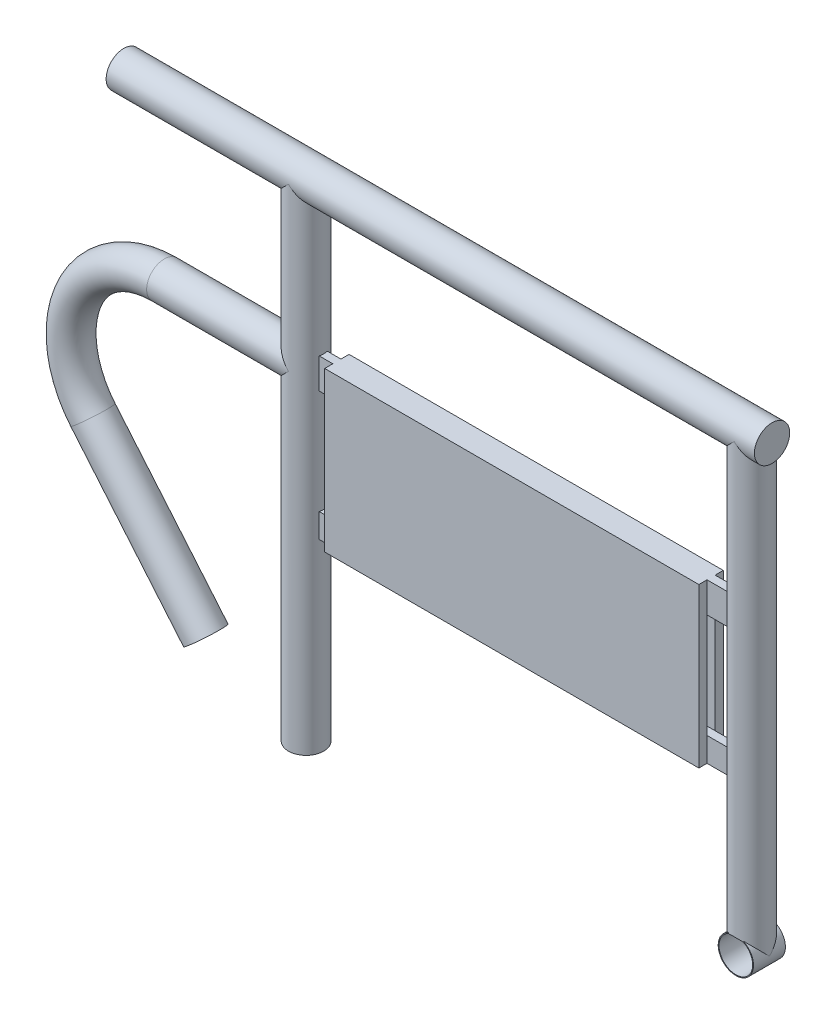
SolidWorks part; units mm, degrees
ref_plane "Front Plane" through (0, 0, 0) normal (0, 0, 1) x (1, 0, 0)
ref_plane "Top Plane" through (0, 0, 0) normal (0, 1, 0) x (1, 0, 0)
ref_plane "Right Plane" through (0, 0, 0) normal (1, 0, 0) x (0, 0, -1)
sketch "Sketch1" plane through (0, 0, 0) normal (0, 1, 0) x (1, 0, 0)
  circle A0 centre (0, 0) radius 11.065
  circle A1 centre (279.4, 0) radius 11.065
  dimension "D1" = 22.13
  dimension "D2" = 22.13
  dimension "D3" = 279.4
extrude "Extrude1" add sketch "Sketch1" along normal blind 279.4
sketch "Sketch2" plane through (0, 0, 0) normal (1, 0, 0) x (0, 0, -1)
  line L0 (11.065, 279.4) -> (-11.065, 279.4) construction
  circle A0 centre (0, 279.4) radius 11.065
extrude "Extrude2" add sketch "Sketch2" along normal blind 292.1 and the other way blind 114.3
sketch "Sketch3" plane through (-114.3, 0, 0) normal (-1, 0, 0) x (0, 0, 1)
  circle A0 centre (0, 177.8) radius 11.065
  circle A1 centre (0, 279.4) radius 11.065 construction
  dimension "D1" = 101.6
extrude "Extrude3" add sketch "Sketch3" against normal blind 114.3
sketch "Sketch5" plane through (0, 0, 0) normal (0, 0, 1) x (1, 0, 0)
  line L0 (-114.3, 188.865) -> (-114.3, 166.735) construction
  line L1 (-139.7, 188.865) -> (-88.9, 188.865)
  line L2 (-139.7, 188.865) -> (-139.7, 166.735)
  line L3 (-139.7, 166.735) -> (-88.9, 166.735)
  line L4 (-88.9, 188.865) -> (-88.9, 166.735)
  line L5 (-139.7, 188.865) -> (-88.9, 166.735) construction
  line L6 (-139.7, 166.735) -> (-88.9, 188.865) construction
  line L7 (-114.3, 166.735) -> (-11.065, 166.735) construction
  point P0 (-114.3, 177.8)
  dimension "D1" = 25.4
extrude "Extrude5" cut sketch "Sketch5" against normal through all and the other way through all
sketch "Sketch7" plane through (-88.9, 0, 0) normal (-1, 0, 0) x (0, 0, 1)
  line L0 (0, 119.38) -> (28.8371, 119.38)
  circle A0 centre (0, 177.8) radius 11.065
  dimension "D1" = 58.42
revolve "Revolve-Thin3" add sketch "Sketch7" angle 130 about L0 body kept at (11.065, 0, 0) wall 10
sketch "Sketch10" plane through (-95.5145, 113.8298, 0) normal (0.6428, -0.766, 0) x (0.766, 0.6428, 0)
  circle A0 centre (-49.7854, 0) radius 11.065
extrude "Extrude6" add sketch "Sketch10" along normal blind 110.1
sketch "Sketch11" plane through (0, 0, 0) normal (1, 0, 0) x (0, 0, -1)
  line L1 (2.55, 168.275) -> (-2.55, 168.275)
  line L2 (2.55, 168.275) -> (2.55, 187.325)
  line L3 (2.55, 187.325) -> (-2.55, 187.325)
  line L4 (-2.55, 168.275) -> (-2.55, 187.325)
  line L5 (2.55, 168.275) -> (-2.55, 187.325) construction
  line L6 (2.55, 187.325) -> (-2.55, 168.275) construction
  line L7 (2.55, 87.6717) -> (-2.55, 87.6717)
  line L8 (2.55, 87.6717) -> (2.55, 102.8283)
  line L9 (2.55, 102.8283) -> (-2.55, 102.8283)
  line L10 (-2.55, 87.6717) -> (-2.55, 102.8283)
  line L11 (2.55, 87.6717) -> (-2.55, 102.8283) construction
  line L12 (2.55, 102.8283) -> (-2.55, 87.6717) construction
  point P0 (0, 177.8)
  point P6 (0, 95.25)
  dimension "D1" = 19.05
  dimension "D2" = 5.1
  dimension "D3" = 82.55
extrude "Extrude7" add sketch "Sketch11" along normal blind 279.4
sketch "Sketch12" plane through (0, 0, 2.55) normal (0, 0, 1) x (1, 0, 0)
  line L0 (268.6328, 187.325) -> (10.7672, 187.325) construction
  line L1 (19.2926, 187.325) -> (253.8741, 187.325)
  line L2 (19.2926, 187.325) -> (19.2926, 87.6717)
  line L3 (19.2926, 87.6717) -> (253.8741, 87.6717)
  line L4 (253.8741, 187.325) -> (253.8741, 87.6717)
  line L5 (268.6328, 87.6717) -> (10.7672, 87.6717) construction
extrude "Extrude8" add sketch "Sketch12" along normal blind 5.1
sketch "Sketch13" plane through (0, 0, 0) normal (0, 0, 1) x (1, 0, 0)
  line L0 (268.335, 0) -> (290.465, 0) construction
  circle A0 centre (279.4, 0) radius 11.065
  circle A1 centre (279.4, 0) radius 10.565
  dimension "D1" = 0.5
extrude "Extrude9" add sketch "Sketch13" along normal blind 10 and the other way blind 10
sketch "Sketch14" plane through (0, 0, -10) normal (0, 0, -1) x (-1, 0, 0)
  line L0 (-289.965, 0) -> (-268.835, 0) construction
  circle A0 centre (-279.4, 0) radius 10.565
extrude "Extrude10" cut sketch "Sketch14" against normal through all and the other way through all
sketch "Sketch15" plane through (0, 0, 0) normal (0, -1, 0) x (1, 0, 0)
  circle A0 centre (0, 0) radius 11.065
extrude "Extrude11" add sketch "Sketch15" along normal blind 28.4
mirror "Mirror1" about plane through (0, 0, 0) normal (0, 0, 1) of "Extrude8"
